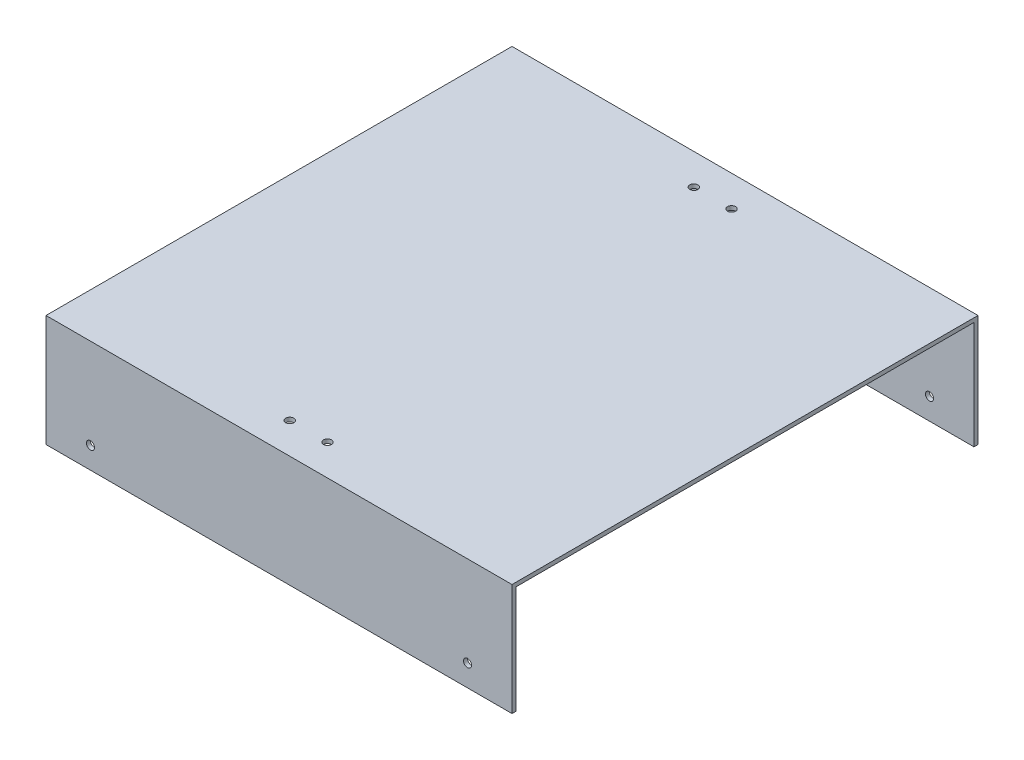
SolidWorks part; units mm, degrees
ref_plane "Front Plane" through (0, 0, 0) normal (0, 0, 1) x (1, 0, 0)
ref_plane "Top Plane" through (0, 0, 0) normal (0, 1, 0) x (1, 0, 0)
ref_plane "Right Plane" through (0, 0, 0) normal (1, 0, 0) x (0, 0, -1)
sketch "Sketch1" plane through (0, 0, 0) normal (0, 1, 0) x (1, 0, 0)
  line L1 (0, 0) -> (173, 0)
  line L2 (0, 0) -> (0, 170)
  line L3 (0, 170) -> (173, 170)
  line L4 (173, 0) -> (173, 170)
  dimension "D1" = 170
  dimension "D2" = 173
extrude "Boss-Extrude1" add sketch "Sketch1" along normal blind 1.5
sketch "Sketch2" plane through (0, 0, 0) normal (0, 0, 1) x (1, 0, 0)
  line L1 (0, 1.5) -> (173, 1.5)
  line L2 (0, 1.5) -> (0, -40)
  line L3 (0, -40) -> (173, -40)
  line L4 (173, 1.5) -> (173, -40)
  dimension "D1" = 41.5
  dimension "D2" = 173
extrude "Boss-Extrude2" add sketch "Sketch2" along normal blind 1.5
sketch "Sketch3" plane through (0, 0, -170) normal (0, 0, -1) x (-1, 0, 0)
  line L1 (-173, 1.5) -> (0, 1.5)
  line L2 (-173, 1.5) -> (-173, -40)
  line L3 (-173, -40) -> (0, -40)
  line L4 (0, 1.5) -> (0, -40)
  dimension "D1" = 41.5
  dimension "D2" = 173
extrude "Boss-Extrude3" add sketch "Sketch3" along normal blind 1.5
sketch "Sketch4" plane through (0, 0, -171.5) normal (0, 0, -1) x (-1, 0, 0)
  line L0 (-173, -40) -> (0, -40) construction
  line L1 (-173, 1.5) -> (-173, -40) construction
  line L2 (0, -40) -> (0, 1.5) construction
  circle A0 centre (-156.5, -32) radius 1.5
  circle A1 centre (-16.5, -32) radius 1.5
  dimension "D1" = 8
  dimension "D2" = 16.5
  dimension "D3" = 16.5
  dimension "D4" = 8
extrude "Cut-Extrude1" cut sketch "Sketch4" against normal blind 1000 and the other way blind 1000
sketch "Sketch5" plane through (0, 1.5, 0) normal (0, 1, 0) x (1, 0, 0)
  line L1 (173, -1.5) -> (173, 171.5) construction
  line L2 (0, 171.5) -> (173, 171.5) construction
  line L3 (173, -1.5) -> (0, -1.5) construction
  circle A0 centre (79, 10) radius 1.5
  circle A1 centre (79, 160) radius 1.5
  circle A2 centre (93, 10) radius 1.5
  circle A3 centre (93, 160) radius 1.5
  dimension "D3" = 80
  dimension "D4" = 11.5
  dimension "D5" = 11.5
  dimension "D6" = 11.5
  dimension "D7" = 11.5
extrude "Cut-Extrude2" cut sketch "Sketch5" against normal blind 5 and the other way blind 5
